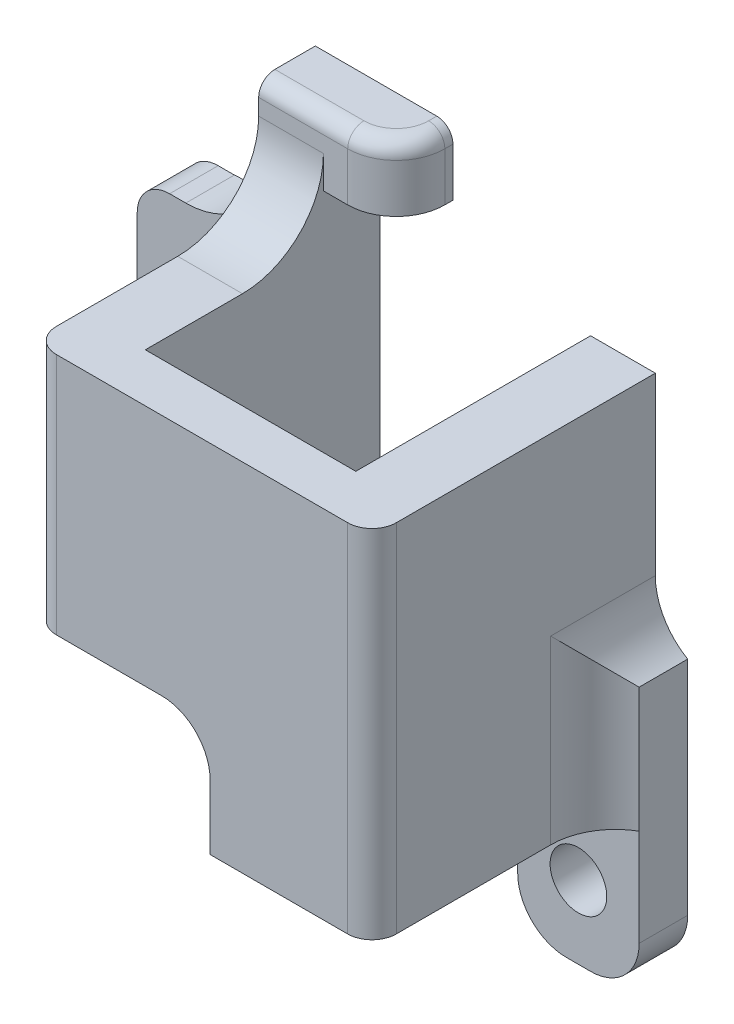
SolidWorks part; units mm, degrees
ref_plane "Front Plane" through (0, 0, 0) normal (0, 0, 1) x (1, 0, 0)
ref_plane "Top Plane" through (0, 0, 0) normal (0, 1, 0) x (1, 0, 0)
ref_plane "Right Plane" through (0, 0, 0) normal (1, 0, 0) x (0, 0, -1)
sketch "Sketch1" plane through (0, 0, 0) normal (0, 0, 1) x (1, 0, 0)
  line L1 (10.5, 7.5) -> (-10.5, 7.5)
  line L2 (10.5, 7.5) -> (10.5, -7.5)
  line L3 (10.5, -7.5) -> (-10.5, -7.5)
  line L4 (-10.5, 7.5) -> (-10.5, -7.5)
  line L5 (10.5, 7.5) -> (-10.5, -7.5) construction
  line L6 (10.5, -7.5) -> (-10.5, 7.5) construction
  point P0 (0, 0)
  dimension "D1" = 21
  dimension "D2" = 15
extrude "Boss-Extrude1" add sketch "Sketch1" against normal blind 3
sketch "Sketch2" plane through (0, 0, -3) normal (0, 0, -1) x (-1, 0, 0)
  line L0 (10.5, -7.5) -> (-10.5, -7.5) construction
  line L1 (10.5, 7.5) -> (6.5, 7.5)
  line L2 (10.5, 7.5) -> (10.5, -7.5)
  line L3 (10.5, -7.5) -> (6.5, -7.5)
  line L4 (6.5, 7.5) -> (6.5, -7.5)
  line L6 (-10.5, 7.5) -> (-6.5, 7.5)
  line L7 (-10.5, 7.5) -> (-10.5, -7.5)
  line L8 (-10.5, -7.5) -> (-6.5, -7.5)
  line L9 (-6.5, 7.5) -> (-6.5, -7.5)
  dimension "D1" = 4
  dimension "D2" = 4
extrude "Boss-Extrude2" add sketch "Sketch2" along normal blind 14.5
sketch "Sketch3" plane through (0, 0, -17.5) normal (0, 0, -1) x (-1, 0, 0)
  line L0 (-6.5, 7.5) -> (6.5, 7.5) construction
  line L1 (10.5, 7.5) -> (6.5, 7.5)
  line L2 (10.5, 7.5) -> (10.5, 14.5)
  line L3 (10.5, 14.5) -> (6.5, 14.5)
  line L4 (6.5, 7.5) -> (6.5, 14.5)
  line L5 (6.5, 10.5) -> (2, 10.5)
  line L6 (6.5, 10.5) -> (6.5, 14.5)
  line L7 (6.5, 14.5) -> (2, 14.5)
  line L8 (2, 10.5) -> (2, 14.5)
  line M10 (10.5, 7.5) -> (6.5, 7.5)
  dimension "D1" = 3
  dimension "D2" = 4
  dimension "D3" = 4.5
  dimension "D4" = 4
extrude "Boss-Extrude3" add sketch "Sketch3" against normal blind 3.5 contours L4 L2 L3 M10 | L8 L5 L4 L7 region at (-8.5, 11, -17.5) region at (-4.25, 12.5, -17.5)
fillet "Fillet1" radius 1 2 edges at (-2, 14.5, -15.75) (-6.25, 14.5, -14)
fillet "Fillet2" radius 3 2 edges at (-2.2929, 14.2071, -14.2929) (-2, 12, -14)
fillet "Fillet3" radius 5 1 edges at (-8.5, 7.5, -14)
sketch "Sketch4" plane through (0, 0, -17.5) normal (0, 0, -1) x (-1, 0, 0)
  line L0 (10.5, -7.5) -> (10.5, 14.5) construction
  line L1 (10.5, 5.0984) -> (18.5, 5.0984)
  line L2 (10.5, 5.0984) -> (10.5, -4.9016)
  line L3 (10.5, -4.9016) -> (18.5, -4.9016)
  line L4 (18.5, 5.0984) -> (18.5, -4.9016)
  circle A0 centre (14.5, 0.0984) radius 1.75
  dimension "D3" = 3.5
  dimension "D5" = 4
  dimension "D1" = 8
  dimension "D2" = 10
  dimension "D4" = 5
extrude "Boss-Extrude4" add sketch "Sketch4" against normal blind 3
fillet "Fillet4" radius 5 2 edges at (-10.5, -4.9016, -16) (-10.5, 5.0984, -16)
fillet "Fillet5" radius 2 2 edges at (-18.5, 5.0984, -16) (-18.5, -4.9016, -16)
sketch "Sketch7" plane through (10.5, 0, 0) normal (1, 0, 0) x (0, 0, -1)
  line L0 (17.5, -7.5) -> (0, -7.5) construction
  line L1 (0, -7.5) -> (3, -7.5)
  line L2 (0, -7.5) -> (0, -14.5)
  line L3 (0, -14.5) -> (3, -14.5)
  line L4 (3, -7.5) -> (3, -14.5)
  line L5 (0, -7.5) -> (0, 7.5) construction
  line L6 (3, -14.5) -> (11, -14.5)
  line L7 (3, -14.5) -> (3, -10.5)
  line L8 (3, -10.5) -> (11, -10.5)
  line L9 (11, -14.5) -> (11, -10.5)
  line M7 (0, -7.5) -> (17.5, -7.5)
  dimension "D1" = 4
  dimension "D2" = 3
  dimension "D3" = 3
  dimension "D4" = 8
  dimension "D5" = 0
extrude "Boss-Extrude5" add sketch "Sketch7" against normal blind 10 contours L4 L2 L3 M7 | L6 L9 L8 L4 region at (10.5, -11, -1.5) region at (10.5, -12.5, -7)
sketch "Sketch8" plane through (0, 0, -3) normal (0, 0, -1) x (-1, 0, 0)
  line L6 (-0.5, -10.5) -> (-10.5, -10.5) construction
  line L7 (-10.5, -7.5) -> (-6.5, -7.5)
  line L8 (-10.5, -7.5) -> (-10.5, -10.5)
  line L9 (-10.5, -10.5) -> (-6.5, -10.5)
  line L10 (-6.5, -7.5) -> (-6.5, -10.5)
extrude "Boss-Extrude6" add sketch "Sketch8" along normal up to surface (8 mm away) up to face at (5.5, -12.5, -11)
sketch "Sketch9" plane through (0, -14.5, 0) normal (0, -1, 0) x (1, 0, 0)
  circle A0 centre (0.5, -11) radius 4.5
  dimension "D1" = 9
extrude "Cut-Extrude1" cut sketch "Sketch9" against normal blind 5
sketch "Sketch10" plane through (0, 0, -11) normal (0, 0, -1) x (-1, 0, 0)
  line L6 (-5, -14.5) -> (-5, -10.5)
  line L7 (-5, -10.5) -> (-6.5, -10.5)
  line L8 (-6.5, -10.5) -> (-6.5, -7.5)
  line L9 (-6.5, -7.5) -> (-10.5, -7.5)
  line L10 (-10.5, -7.5) -> (-10.5, -14.5)
  line L11 (-10.5, -14.5) -> (-5, -14.5)
  line L12 (-5, -14.5) -> (-5, -10.5)
  line L13 (-5, -10.5) -> (-6.5, -10.5)
  line L15 (-6.5, -7.5) -> (-10.5, -7.5)
  line L16 (-10.5, -7.5) -> (-10.5, -14.5)
  line L17 (-10.5, -14.5) -> (-5, -14.5)
  line L18 (-6.5, -10.5) -> (-6.5, -7.5)
  dimension "D1" = 0
extrude "Boss-Extrude7" add sketch "Sketch10" along normal up to surface (6.5 mm away) up to face at (8.5, 0, -17.5)
sketch "Sketch11" plane through (0, 0, -17.5) normal (0, 0, -1) x (-1, 0, 0)
  line L0 (-10.5, -14.5) -> (-5, -14.5) construction
  line L1 (-5, -10.5) -> (-5, -14.5) construction
  line L2 (-5, -14.5) -> (-12.5, -14.5)
  line L3 (-5, -14.5) -> (-5, -23.5)
  line L4 (-5, -23.5) -> (-12.5, -23.5)
  line L5 (-12.5, -14.5) -> (-12.5, -23.5)
  line L7 (-10.5, -14.5) -> (-12.5, -14.5)
  line L8 (-10.5, -14.5) -> (-10.5, -6.795)
  line L9 (-10.5, -6.795) -> (-12.5, -6.795)
  line L10 (-12.5, -14.5) -> (-12.5, -6.795)
  circle A0 centre (-8.75, -19) radius 1.75
  line M6 (-10.5, 7.5) -> (-10.5, -14.5)
  line M7 (-10.5, -14.5) -> (-5, -14.5)
  dimension "D1" = 3.5
  dimension "D2" = 4.5
  dimension "D3" = 3.75
  dimension "D6" = 4.5
  dimension "D8" = 3.75
  dimension "D4" = 2
  dimension "D5" = 2
  dimension "D7" = 9
extrude "Boss-Extrude8" add sketch "Sketch11" against normal blind 3 contours L2 L5 L4 L3 A0 M7 | L10 L2 L9 M6 region at (5.1172, -19, -17.5) region at (11.5, -10.6475, -17.5)
fillet "Fillet6" radius 4 1 edges at (10.5, -10.6475, -14.5)
fillet "Fillet7" radius 4 1 edges at (10.5, -6.795, -14.2679)
fillet "Fillet8" radius 3 2 edges at (12.5, -23.5, -16) (5, -23.5, -16)
fillet "Fillet9" radius 3 2 edges at (0.5, -7.5, -1.5) (0.5, -12.5, -6.5)
fillet "Fillet10" radius 1.5 2 edges at (-10.5, 0, 0) (10.5, -3.5, 0)
